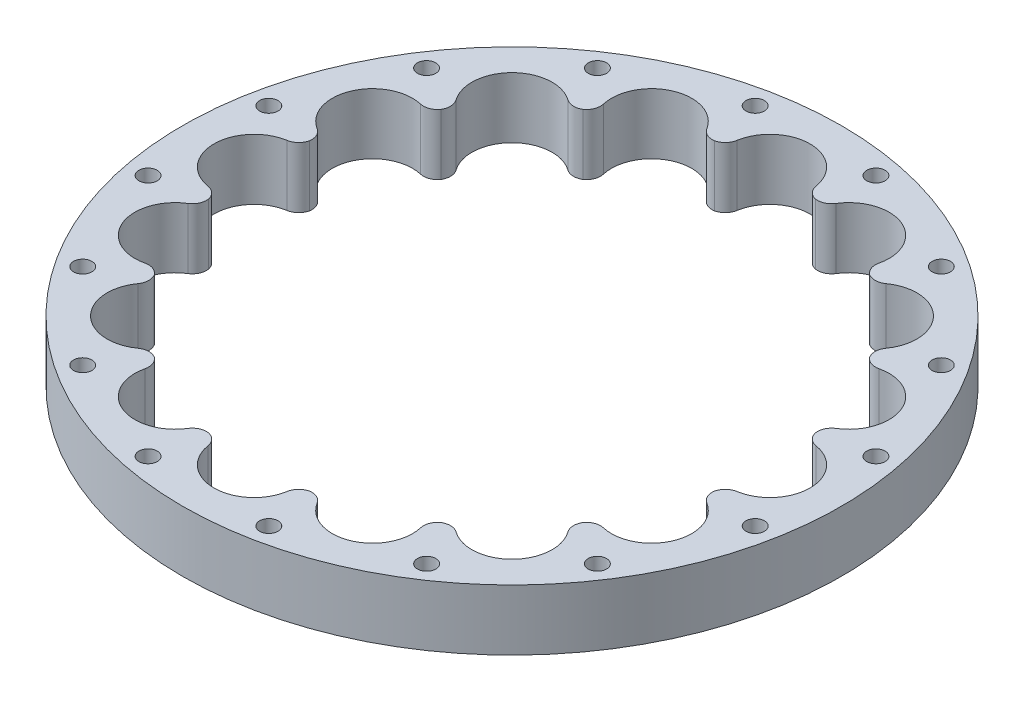
SolidWorks part; units mm, degrees
ref_plane "Front Plane" through (0, 0, 0) normal (0, 0, 1) x (1, 0, 0)
ref_plane "Top Plane" through (0, 0, 0) normal (0, 1, 0) x (1, 0, 0)
ref_plane "Right Plane" through (0, 0, 0) normal (1, 0, 0) x (0, 0, -1)
sketch "Sketch1" plane through (0, 0, 0) normal (0, 1, 0) x (1, 0, 0)
  line L0 (-10.5349, 52.9624) -> (0, 0) construction
  line L1 (0, 0) -> (-17.2208, 41.5746) construction
  circle A0 centre (0, 0) radius 45
  circle A1 centre (0, 45) radius 7
  circle A2 centre (17.2208, 41.5746) radius 7
  circle A3 centre (31.8198, 31.8198) radius 7
  circle A4 centre (41.5746, 17.2208) radius 7
  circle A5 centre (45, 0) radius 7
  circle A6 centre (41.5746, -17.2208) radius 7
  circle A7 centre (31.8198, -31.8198) radius 7
  circle A8 centre (17.2208, -41.5746) radius 7
  circle A9 centre (0, -45) radius 7
  circle A10 centre (-17.2208, -41.5746) radius 7
  circle A11 centre (-31.8198, -31.8198) radius 7
  circle A12 centre (0, 0) radius 57.5
  circle A13 centre (0, 0) radius 54 construction
  circle A14 centre (-10.5349, 52.9624) radius 1.6
  circle A15 centre (10.5349, 52.9624) radius 1.6
  circle A16 centre (30.0008, 44.8994) radius 1.6
  circle A17 centre (44.8994, 30.0008) radius 1.6
  circle A18 centre (52.9624, 10.5349) radius 1.6
  circle A19 centre (52.9624, -10.5349) radius 1.6
  circle A20 centre (44.8994, -30.0008) radius 1.6
  circle A21 centre (30.0008, -44.8994) radius 1.6
  circle A22 centre (10.5349, -52.9624) radius 1.6
  circle A23 centre (-10.5349, -52.9624) radius 1.6
  circle A24 centre (-30.0008, -44.8994) radius 1.6
  circle A25 centre (-44.8994, -30.0008) radius 1.6
  circle A26 centre (-41.5746, -17.2208) radius 7
  circle A27 centre (-45, 0) radius 7
  circle A28 centre (-41.5746, 17.2208) radius 7
  circle A29 centre (-31.8198, 31.8198) radius 7
  circle A30 centre (-17.2208, 41.5746) radius 7
  circle A31 centre (-52.9624, -10.5349) radius 1.6
  circle A32 centre (-52.9624, 10.5349) radius 1.6
  circle A33 centre (-44.8994, 30.0008) radius 1.6
  circle A34 centre (-30.0008, 44.8994) radius 1.6
  point P27 (0, 0)
  point P54 (0, 0)
  point P71 (0, 0)
  dimension "D1" = 90
  dimension "D2" = 14
  dimension "D4" = 115
  dimension "D5" = 108
  dimension "D6" = 3.2
  dimension "D8" = 11.25
  dimension "D3" = 16
  dimension "D7" = 16
extrude "Boss-Extrude1" add sketch "Sketch1" along normal blind 10.6 contours A12 A25 A24 A23 A22 A21 A20 A19 A18 A17 A16 A15 A14 A11 A0 A1 A2 A3 A4 A5 A6 A7 A8 A9 A10 region at (-55.8737, 0, 0)
fillet "Fillet1" radius 2.5 32 edges at (38.4009, 5.3, -23.46) (36.3696, 5.3, -26.5001) (44.4556, 5.3, -6.9788) (43.7422, 5.3, -10.5648) (44.4556, 5.3, 6.9788) (43.7422, 5.3, 10.5648) (38.4009, 5.3, 23.46) (36.3696, 5.3, 26.5001) (26.5001, 5.3, 36.3696) (23.46, 5.3, 38.4009) (6.9788, 5.3, 44.4556) (10.5648, 5.3, 43.7422) (-6.9788, 5.3, 44.4556) (-10.5648, 5.3, 43.7422) (-23.46, 5.3, 38.4009) (-26.5001, 5.3, 36.3696) (26.5001, 5.3, -36.3696) (23.46, 5.3, -38.4009) (10.5648, 5.3, -43.7422) (6.9788, 5.3, -44.4556) (-6.9788, 5.3, -44.4556) (-36.3696, 5.3, 26.5001) (-10.5648, 5.3, -43.7422) (-23.46, 5.3, -38.4009) (-26.5001, 5.3, -36.3696) (-36.3696, 5.3, -26.5001) (-38.4009, 5.3, -23.46) (-43.7422, 5.3, -10.5648) (-44.4556, 5.3, -6.9788) (-44.4556, 5.3, 6.9788) (-43.7422, 5.3, 10.5648) (-38.4009, 5.3, 23.46)
